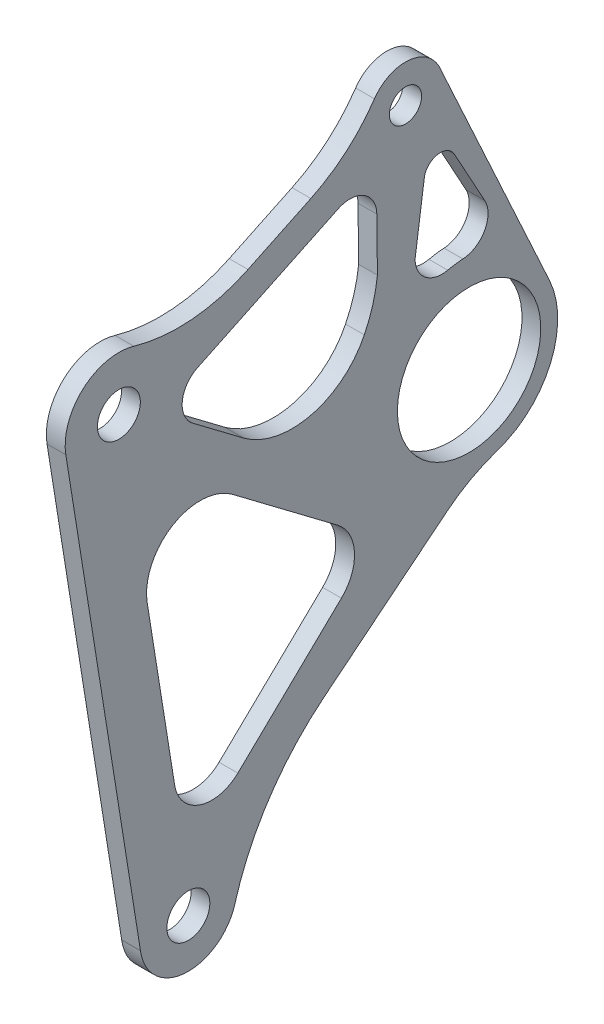
SolidWorks part; units mm, degrees
ref_plane "Płaszczyzna XY" through (0, 0, 0) normal (0, 0, 1) x (1, 0, 0)
ref_plane "Płaszczyzna XZ" through (0, 0, 0) normal (0, 1, 0) x (1, 0, 0)
ref_plane "Płaszczyzna YZ" through (0, 0, 0) normal (1, 0, 0) x (0, 0, -1)
sketch "Szkic7" plane through (-10.5401, 0, 0) normal (-1, 0, 0) x (0, 0, 1)
  line L1 (-48.3801, 69.9121) -> (90.8866, 69.9121)
  line L2 (-48.3801, 69.9121) -> (-48.3801, -91.017)
  line L3 (-48.3801, -91.017) -> (90.8866, -91.017)
  line L4 (90.8866, 69.9121) -> (90.8866, -91.017)
  circle A0 centre (0, 0) radius 12 construction
  dimension "D1" = 160.9291
  dimension "D2" = 114.6651
  dimension "D3" = 139.2667
  dimension "D4" = 103.0763
extrude "Dodanie-wyciągnięcie2" add sketch "Szkic7" along normal blind 3.5
sketch "Szkic8" plane through (-14.0401, 0, 0) normal (-1, 0, 0) x (0, 0, 1)
  line L2 (-48.3801, 69.9121) -> (-48.3801, -91.017) construction
  line L3 (-48.3801, -91.017) -> (90.8866, -91.017) construction
  circle A0 centre (0, 0) radius 13.35
  circle A1 centre (11.8446, 48.5768) radius 3
  circle A2 centre (65.2198, 25.424) radius 4
  circle A3 centre (52.2787, -61.8704) radius 4
  dimension "D1" = 6
  dimension "D2" = 26.7
  dimension "D3" = 8
  dimension "D4" = 48.3801
  dimension "D5" = 60.2247
  dimension "D6" = 100.6587
  dimension "D7" = 113.5999
  dimension "D8" = 29.1466
  dimension "D9" = 91.017
  dimension "D10" = 116.441
  dimension "D11" = 139.5938
extrude "Wytnij-wyciągnięcie4" cut sketch "Szkic8" against normal through all
sketch "Szkic9" plane through (-14.0401, 0, 0) normal (-1, 0, 0) x (0, 0, 1)
  line L0 (-13.3821, -14.8633) -> (46.2567, -68.5589)
  line L1 (5.7089, 51.9462) -> (-17.5306, 9.6269)
  line L4 (61.1958, -63.0892) -> (75.0944, 23.8453)
  line L5 (-54.0942, 129.567) -> (99.4185, 129.567)
  line L6 (-54.0942, 129.567) -> (-54.0942, -98.6712)
  line L7 (-54.0942, -98.6712) -> (99.4185, -98.6712)
  line L8 (99.4185, 129.567) -> (99.4185, -98.6712)
  line L9 (14.5194, 55.0456) -> (68.7203, 34.7913)
  arc A0 (-17.5306, 9.6269) -> (-13.3821, -14.8633) centre (0, 0) ccw
  arc A1 (14.5194, 55.0456) -> (5.7089, 51.9462) centre (11.8446, 48.5768) ccw
  arc A3 (46.2567, -68.5589) -> (61.1958, -63.0892) centre (52.2787, -61.8704) ccw
  circle A4 centre (0, 0) radius 13.35 construction
  arc A5 (75.0944, 23.8453) -> (68.7203, 34.7913) centre (65.2198, 25.424) ccw
  dimension "D1" = 40
  dimension "D2" = 14
  dimension "D3" = 9
  dimension "D13" = 20
  dimension "D5" = 228.2382
  dimension "D6" = 158.3717
  dimension "D7" = 153.5127
  dimension "D8" = 163.3145
  dimension "D9" = 5.7089
  dimension "D10" = 11.8446
  dimension "D11" = 14.5194
  dimension "D12" = 61.1958
extrude "Wytnij-wyciągnięcie5" cut sketch "Szkic9" against normal through all
sketch "Szkic14" plane through (-10.5401, 0, 0) normal (1, 0, 0) x (0, 0, -1)
  line L1 (-64.0841, 18.3204) -> (-52.715, -52.7924)
  line L4 (-5.6266, 41.4089) -> (0.3299, 30.5619)
  line L7 (-61.1958, -63.0892) -> (-75.0944, 23.8453) construction
  line L8 (-32.632, -33.4541) -> (-18.9938, -20.3216)
  line L9 (-52.715, -52.7924) -> (-32.632, -33.4541)
  line L11 (0.3299, 30.5619) -> (7.9338, 16.7152)
  line L13 (-64.0841, 18.3204) -> (-5.6266, 41.4089)
  line L14 (-18.9938, -20.3216) -> (-23.4974, -7.53)
  arc A2 (-23.4974, -7.53) -> (-16.7223, 7.9188) centre (246.4773, -116.7184) cw
  arc A3 (7.9338, 16.7152) -> (-16.7223, 7.9188) centre (0, 0) ccw
  dimension "D8" = 15.7664
  dimension "D1" = 291.2189
  dimension "D2" = 18.5025
  dimension "D3" = 10
  dimension "D13" = 35.1048
  dimension "D14" = 61.0289
  dimension "D15" = 99.1208
  dimension "D18" = 86.8793
sketch "Szkic15" plane through (-10.5401, 0, 0) normal (1, 0, 0) x (0, 0, -1)
  line L8 (-52.2787, -61.8704) -> (0, 0) construction
  line L9 (-46.2474, -68.5504) -> (13.3821, -14.8633)
  line L10 (13.3821, -14.8633) -> (-46.2567, -68.5589) construction
  line L11 (-46.4699, -54.9959) -> (-2.9111, -19.787)
  arc A3 (-2.9111, -19.787) -> (13.3821, -14.8633) centre (0, 0) ccw
  arc A4 (-46.2474, -68.5504) -> (-46.4699, -54.9959) centre (-52.2787, -61.8704) ccw
  dimension "D2" = 20
extrude "Wytnij-wyciągnięcie14" cut sketch "Szkic14" against normal through all
sketch "Szkic18" plane through (-10.5401, 0, 0) normal (1, 0, 0) x (0, 0, -1)
  line L2 (-56.1447, 29.6243) -> (-18.7596, 47.489)
  line L6 (-64.4986, 23.4157) -> (-11.8446, 48.5768) construction
  line L8 (-14.3453, 55.1149) -> (-18.275, 65.3894)
  line L9 (-18.275, 65.3894) -> (-73.4583, 44.283)
  line L10 (-73.4583, 44.283) -> (-68.8407, 34.7454)
  arc A1 (-14.3453, 55.1149) -> (-18.7596, 47.489) centre (-11.8446, 48.5768) ccw
  arc A2 (-56.1447, 29.6243) -> (-68.8407, 34.7454) centre (-65.2198, 25.424) ccw
  dimension "D2" = 7
  dimension "D6" = 10
  dimension "D3" = 6.218
  dimension "D4" = 8.7186
  dimension "D5" = 4
  dimension "D7" = 12.6484
  dimension "D8" = 13.1329
  dimension "D9" = 50.5181
  dimension "D10" = 63.2141
  dimension "D11" = 2.8741
extrude "Wytnij-wyciągnięcie15" cut sketch "Szkic18" against normal through all
fillet "Zaokrąglenie11" radius 30 2 edges at (-12.2901, 47.4891, 18.7596) (-12.2901, 29.6243, 56.1447)
sketch "Szkic19" plane through (-10.5401, 0, 0) normal (1, 0, 0) x (0, 0, -1)
  line L4 (-58.946, 22.7776) -> (-66.3228, 19.747)
  line L8 (-20.2273, -16.0087) -> (-16.0354, -9.5644)
  line L9 (-16.0354, -9.5644) -> (-58.946, 22.7776)
  line L10 (-20.2273, -16.0087) -> (-66.7206, 19.0337)
  line L11 (-66.7206, 19.0337) -> (-66.3228, 19.747)
extrude "Dodanie-wyciągnięcie5" add sketch "Szkic19" against normal blind 3.5
fillet "Zaokrąglenie14" radius 5 1 edges at (-12.2901, 16.7152, -7.9338)
sketch "Szkic21" plane through (-10.5401, 0, 0) normal (1, 0, 0) x (0, 0, -1)
  line L1 (-57.7473, 22.2086) -> (-14.8083, 42.7273)
  line L3 (-5.6266, 41.4089) -> (-7.0855, 44.0656)
  line L9 (-41.1695, 36.7803) -> (-29.4659, 42.3729) construction
  line L11 (2.9103, 25.8631) -> (-5.6266, 41.4089) construction
  line L14 (-56.8324, 21.1846) -> (-58.0182, 22.095)
  line L15 (-57.7473, 22.2086) -> (-58.0182, 22.095)
  line L16 (-56.8324, 21.1846) -> (-5.6266, 41.4089)
  arc A0 (-14.8083, 42.7273) -> (-7.0855, 44.0656) centre (-11.8446, 48.5768) ccw
  dimension "D2" = 6.5574
  dimension "D1" = 6
  dimension "D5" = 47.5897
extrude "Wytnij-wyciągnięcie17" cut sketch "Szkic21" against normal through all
sketch "Szkic22" plane through (-14.0401, 0, 0) normal (-1, 0, 0) x (0, 0, 1)
  line L0 (17.3122, 44.6278) -> (16.8817, 7.573)
  line L1 (10.3117, 44.6278) -> (9.9203, 10.9322)
  line L2 (10.3117, 44.6278) -> (17.3122, 44.6278)
  line L4 (16.8817, 7.573) -> (9.9203, 10.9322)
  arc A0 (16.7223, 7.9188) -> (1.1591, 18.4662) centre (0, 0) ccw construction
  dimension "D1" = 7
extrude "Dodanie-wyciągnięcie6" add sketch "Szkic22" against normal blind 3.5
fillet "Zaokrąglenie24" radius 5 1 edges at (-12.2901, 15.5839, 9.9743)
sketch "Szkic24" plane through (-10.5401, 0, 0) normal (1, 0, 0) x (0, 0, -1)
  line L0 (-36.8164, 1.7532) -> (-22.7475, -7.1897)
  line L7 (-16.8818, 7.5814) -> (-17.2764, 41.5479) construction
  line L8 (-16.8972, -9.8835) -> (-13.2678, 11.5067)
  line L13 (-17.0703, 23.8063) -> (-13.2678, 11.5067)
  line L14 (-22.7475, -7.1897) -> (-16.8972, -9.8835)
  arc A3 (-17.0703, 23.8063) -> (-36.8164, 1.7532) centre (-42.3567, 26.5807) cw
  dimension "D2" = 7.559
  dimension "D5" = 11.1884
  dimension "D9" = 58.6754
extrude "Dodanie-wyciągnięcie7" add sketch "Szkic24" against normal blind 3.5
extrude "Wytnij-wyciągnięcie19" cut sketch "Szkic15" against normal blind 10
fillet "Zaokrąglenie45" radius 50 1 edges at (-12.2901, -54.9959, 46.4699)
fillet "Zaokrąglenie46" radius 5 1 edges at (-12.2901, -63.0892, 61.1958)
fillet "Zaokrąglenie49" radius 7 1 edges at (-12.2901, -52.7924, 52.715)
sketch "Szkic26" plane through (-10.5401, 0, 0) normal (1, 0, 0) x (0, 0, -1)
  line L0 (-7.0855, 44.0656) -> (-10.0592, 22.8934)
  line L1 (-10.0592, 22.8934) -> (-14.3044, 31.1384)
  line L2 (-14.3044, 31.1384) -> (-12.5815, 43.4048)
  line L3 (-12.5815, 43.4048) -> (-7.0855, 44.0656)
  dimension "D1" = 6.8727
  dimension "D2" = 8.5955
  dimension "D3" = 9.1193
extrude "Dodanie-wyciągnięcie8" add sketch "Szkic26" against normal blind 3.5
fillet "Zaokrąglenie61" radius 3 1 edges at (-12.2901, 44.0656, 7.0855)
fillet "Zaokrąglenie62" radius 5 1 edges at (-12.2901, 41.5479, 17.2764)
sketch "Szkic28" plane through (-10.5401, 0, 0) normal (1, 0, 0) x (0, 0, -1)
  line L1 (14.9957, 6.8833) -> (-5.4828, 51.497)
  line L3 (35.6626, -24.3394) -> (-2.9111, -30.1882)
  line L4 (-2.9111, -30.1882) -> (-2.9111, -19.787)
  line L5 (-5.4828, 51.497) -> (18.5573, 44.467)
  line L6 (18.5573, 44.467) -> (35.6626, -24.3394)
  line L8 (-2.9111, -19.787) -> (1.1438, -16.4603)
  arc A1 (1.1438, -16.4603) -> (14.9957, 6.8833) centre (0, 0) ccw
  circle A2 centre (-11.8446, 48.5768) radius 7
  dimension "D1" = 16.5
  dimension "D3" = 14
  dimension "D6" = 13.3099
  dimension "D7" = 19.1587
  dimension "D8" = 87.9651
extrude "Wytnij-wyciągnięcie21" cut sketch "Szkic28" against normal through all
fillet "Zaokrąglenie69" radius 30 1 edges at (-12.2901, -16.4603, -1.1438)
fillet "Zaokrąglenie72" radius 10 2 edges at (-12.2901, -20.3216, 18.9938) (-12.2901, 16.872, 63.8525)
fillet "Zaokrąglenie75" radius 5 1 edges at (-12.2901, 22.095, 58.0182)
fillet "Zaokrąglenie76" radius 8 1 edges at (-12.2901, -15.7162, 20.6153)
fillet "Zaokrąglenie77" radius 15 1 edges at (-12.2901, 3.0288, 32.7438)
